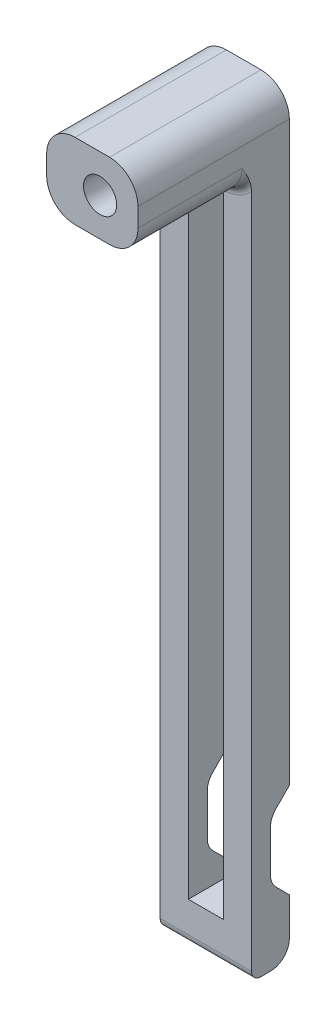
SolidWorks part; units mm, degrees
ref_plane "Ebene vorne" through (0, 0, 0) normal (0, 0, 1) x (1, 0, 0)
ref_plane "Ebene oben" through (0, 0, 0) normal (0, 1, 0) x (1, 0, 0)
ref_plane "Ebene rechts" through (0, 0, 0) normal (1, 0, 0) x (0, 0, -1)
sketch "body" plane through (0, 0, 0) normal (0, 0, 1) x (1, 0, 0)
  line L1 (-4.825, 40) -> (4.825, 40)
  line L2 (-4.825, 40) -> (-4.825, -40)
  line L3 (-4.825, -40) -> (4.825, -40)
  line L4 (4.825, 40) -> (4.825, -40)
  line L5 (-4.825, 40) -> (4.825, -40) construction
  line L6 (-4.825, -40) -> (4.825, 40) construction
  point P0 (0, 0)
  dimension "D1" = 80
  dimension "D2" = 9.65
extrude "body_" add sketch "body" along normal mid plane 4
sketch "Skizze2" plane through (0, 0, 2) normal (0, 0, 1) x (1, 0, 0)
  line L0 (0, 40) -> (0, -40) construction
  line L1 (4.825, 40) -> (-4.825, 40) construction
  line L2 (-4.825, -40) -> (4.825, -40) construction
  line L4 (-1.85, 30.75) -> (1.85, 30.75)
  line L5 (-1.85, 30.75) -> (-1.85, -35.75)
  line L6 (-1.85, -35.75) -> (1.85, -35.75)
  line L7 (1.85, 30.75) -> (1.85, -35.75)
  line L8 (-1.85, 30.75) -> (1.85, -35.75) construction
  line L9 (-1.85, -35.75) -> (1.85, 30.75) construction
  point P6 (0, -2.5)
  dimension "D1" = 66.5
  dimension "D2" = 3.7
  dimension "D3" = 37.5
extrude "rut" cut sketch "Skizze2" against normal through all
sketch "spare" plane through (4.825, 0, 0) normal (1, 0, 0) x (0, 0, -1)
  line L0 (2, -24) -> (0, -26)
  line L1 (2, -40) -> (2, 40) construction
  line L2 (0, -26) -> (0, -32)
  line L3 (0, -32) -> (2, -34)
  line L4 (2, -34) -> (2, -24)
  line L6 (2, -29) -> (-2, -29) construction
  line L7 (-2, 40) -> (-2, -40) construction
  line L8 (-2, -40) -> (2, -40) construction
  point P6 (0, -29)
  dimension "D1" = 45
  dimension "D2" = 6
  dimension "D3" = 45
  dimension "D4" = 2
  dimension "D5" = 10
  dimension "D6" = 11
extrude "notch" cut sketch "spare" against normal through all
fillet "Verrundung3" radius 2 4 edges at (-3.3375, -32, 0) (-3.3375, -26, 0) (3.3375, -26, 0) (3.3375, -32, 0)
fillet "Verrundung4" radius 1 1 edges at (0, -40, 2)
fillet "Verrundung5" radius 1 2 edges at (-3.3375, -34, -2) (-3.3375, -24, -2)
sketch "Skizze4" plane through (0, 0, 2) normal (0, 0, 1) x (1, 0, 0)
  line L0 (-4.825, 40) -> (-4.825, -39) construction
  line L1 (-4.825, 32) -> (4.825, 32)
  line L2 (-4.825, 32) -> (-4.825, 40)
  line L3 (-4.825, 40) -> (4.825, 40)
  line L4 (4.825, 32) -> (4.825, 40)
  dimension "D1" = 8
extrude "Aufsatz-Linear austragen1" add sketch "Skizze4" along normal blind 12
fillet "Verrundung6" radius 2 1 edges at (0, -40, -2)
sketch "Skizze5" plane through (0, 0, 14) normal (0, 0, 1) x (1, 0, 0)
  line L0 (4.825, 40) -> (-4.825, 40) construction
  line L1 (-4.825, 32) -> (4.825, 32) construction
  line L3 (4.825, 32) -> (4.825, 40) construction
  line L4 (-4.825, 40) -> (-4.825, 32) construction
  circle A0 centre (0.825, 36) radius 1.75
  point P5 (4.825, 36)
  dimension "D1" = 8
  dimension "D5" = 3.5
  dimension "D2" = 4
  dimension "D3" = 5.65
  dimension "D4" = 4
extrude "loch" cut sketch "Skizze5" against normal through all
fillet "Verrundung7" radius 3 4 edges at (-4.825, 40, 6) (4.825, 40, 6) (-4.825, 32, 8) (4.825, 32, 8)
fillet "Verrundung8" radius 1 3 edges at (-3.9463, 32.8787, 2) (3.9463, 32.8787, 2) (0, 32, 2)
